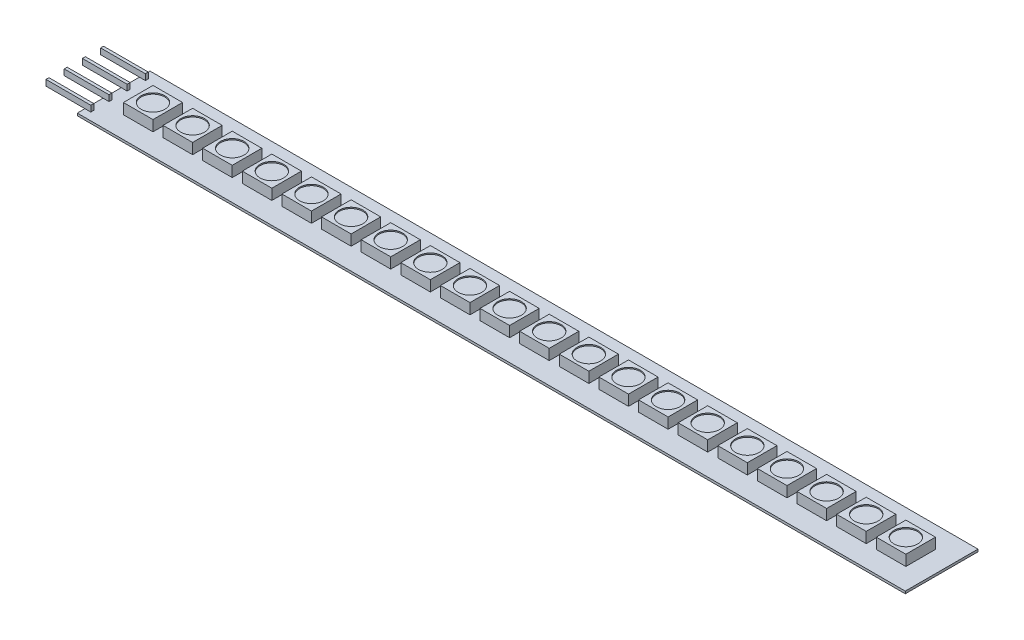
SolidWorks part; units mm, degrees
ref_plane "前基準面" through (0, 0, 0) normal (0, 0, 1) x (1, 0, 0)
ref_plane "上基準面" through (0, 0, 0) normal (0, 1, 0) x (1, 0, 0)
ref_plane "右基準面" through (0, 0, 0) normal (1, 0, 0) x (0, 0, -1)
sketch "草圖1" plane through (0, 0, 0) normal (0, 1, 0) x (1, 0, 0)
  line L1 (0, 0) -> (140, 0)
  line L2 (0, 0) -> (0, 12.3)
  line L3 (0, 12.3) -> (140, 12.3)
  line L4 (140, 0) -> (140, 12.3)
  dimension "D1" = 140
  dimension "D2" = 12.3
extrude "填料-伸長1" add sketch "草圖1" along normal blind 0.4
sketch "草圖2" plane through (0, 0.4, 0) normal (0, 1, 0) x (1, 0, 0)
  line L0 (10, 12.3) -> (10, 0)
  line L1 (140, 12.3) -> (0, 12.3) construction
  line L2 (0, 0) -> (140, 0) construction
  line L3 (0, 12.3) -> (0, 0) construction
  line L4 (16.7, 12.3) -> (16.7, 0)
  line L5 (16.7, 12.3) -> (10, 0) construction
  line L6 (10, 0) -> (10, 12.3) construction
  line L7 (10, 12.3) -> (16.7, 0) construction
  line L8 (9.15, 8.65) -> (4.15, 8.65)
  line L9 (10.85, 3.65) -> (15.85, 3.65)
  line L10 (10.85, 3.65) -> (10.85, 8.65)
  line L11 (10.85, 8.65) -> (15.85, 8.65)
  line L12 (15.85, 3.65) -> (15.85, 8.65)
  line L13 (10.85, 3.65) -> (15.85, 8.65) construction
  line L14 (10.85, 8.65) -> (15.85, 3.65) construction
  line L15 (4.15, 3.65) -> (4.15, 8.65)
  line L16 (9.15, 3.65) -> (4.15, 3.65)
  line L17 (9.15, 3.65) -> (9.15, 8.65)
  line L18 (17.55, 3.65) -> (17.55, 8.65)
  line L19 (17.55, 3.65) -> (22.55, 3.65)
  line L20 (22.55, 3.65) -> (22.55, 8.65)
  line L21 (17.55, 8.65) -> (22.55, 8.65)
  line L22 (23.4, 12.3) -> (23.4, 0)
  line L23 (24.25, 3.65) -> (24.25, 8.65)
  line L24 (24.25, 3.65) -> (29.25, 3.65)
  line L25 (29.25, 3.65) -> (29.25, 8.65)
  line L26 (24.25, 8.65) -> (29.25, 8.65)
  line L27 (30.1, 12.3) -> (30.1, 0)
  line L28 (30.95, 3.65) -> (30.95, 8.65)
  line L29 (30.95, 3.65) -> (35.95, 3.65)
  line L30 (35.95, 3.65) -> (35.95, 8.65)
  line L31 (30.95, 8.65) -> (35.95, 8.65)
  line L32 (36.8, 12.3) -> (36.8, 0)
  line L33 (37.65, 3.65) -> (37.65, 8.65)
  line L34 (37.65, 3.65) -> (42.65, 3.65)
  line L35 (42.65, 3.65) -> (42.65, 8.65)
  line L36 (37.65, 8.65) -> (42.65, 8.65)
  line L37 (43.5, 12.3) -> (43.5, 0)
  line L38 (44.35, 3.65) -> (44.35, 8.65)
  line L39 (44.35, 3.65) -> (49.35, 3.65)
  line L40 (49.35, 3.65) -> (49.35, 8.65)
  line L41 (44.35, 8.65) -> (49.35, 8.65)
  line L42 (50.2, 12.3) -> (50.2, 0)
  line L43 (51.05, 3.65) -> (51.05, 8.65)
  line L44 (51.05, 3.65) -> (56.05, 3.65)
  line L45 (56.05, 3.65) -> (56.05, 8.65)
  line L46 (51.05, 8.65) -> (56.05, 8.65)
  line L47 (56.9, 12.3) -> (56.9, 0)
  line L48 (57.75, 3.65) -> (57.75, 8.65)
  line L49 (57.75, 3.65) -> (62.75, 3.65)
  line L50 (62.75, 3.65) -> (62.75, 8.65)
  line L51 (57.75, 8.65) -> (62.75, 8.65)
  line L52 (63.6, 12.3) -> (63.6, 0)
  line L53 (64.45, 3.65) -> (64.45, 8.65)
  line L54 (64.45, 3.65) -> (69.45, 3.65)
  line L55 (69.45, 3.65) -> (69.45, 8.65)
  line L56 (64.45, 8.65) -> (69.45, 8.65)
  line L57 (70.3, 12.3) -> (70.3, 0)
  line L58 (71.15, 3.65) -> (71.15, 8.65)
  line L59 (71.15, 3.65) -> (76.15, 3.65)
  line L60 (76.15, 3.65) -> (76.15, 8.65)
  line L61 (71.15, 8.65) -> (76.15, 8.65)
  line L62 (77, 12.3) -> (77, 0)
  line L63 (77.85, 3.65) -> (77.85, 8.65)
  line L64 (77.85, 3.65) -> (82.85, 3.65)
  line L65 (82.85, 3.65) -> (82.85, 8.65)
  line L66 (77.85, 8.65) -> (82.85, 8.65)
  line L67 (83.7, 12.3) -> (83.7, 0)
  line L68 (84.55, 3.65) -> (84.55, 8.65)
  line L69 (84.55, 3.65) -> (89.55, 3.65)
  line L70 (89.55, 3.65) -> (89.55, 8.65)
  line L71 (84.55, 8.65) -> (89.55, 8.65)
  line L72 (90.4, 12.3) -> (90.4, 0)
  line L73 (91.25, 3.65) -> (91.25, 8.65)
  line L74 (91.25, 3.65) -> (96.25, 3.65)
  line L75 (96.25, 3.65) -> (96.25, 8.65)
  line L76 (91.25, 8.65) -> (96.25, 8.65)
  line L77 (97.1, 12.3) -> (97.1, 0)
  line L78 (97.95, 3.65) -> (97.95, 8.65)
  line L79 (97.95, 3.65) -> (102.95, 3.65)
  line L80 (102.95, 3.65) -> (102.95, 8.65)
  line L81 (97.95, 8.65) -> (102.95, 8.65)
  line L82 (103.8, 12.3) -> (103.8, 0)
  line L83 (104.65, 3.65) -> (104.65, 8.65)
  line L84 (104.65, 3.65) -> (109.65, 3.65)
  line L85 (109.65, 3.65) -> (109.65, 8.65)
  line L86 (104.65, 8.65) -> (109.65, 8.65)
  line L87 (110.5, 12.3) -> (110.5, 0)
  line L88 (111.35, 3.65) -> (111.35, 8.65)
  line L89 (111.35, 3.65) -> (116.35, 3.65)
  line L90 (116.35, 3.65) -> (116.35, 8.65)
  line L91 (111.35, 8.65) -> (116.35, 8.65)
  line L92 (117.2, 12.3) -> (117.2, 0)
  line L93 (118.05, 3.65) -> (118.05, 8.65)
  line L94 (118.05, 3.65) -> (123.05, 3.65)
  line L95 (123.05, 3.65) -> (123.05, 8.65)
  line L96 (118.05, 8.65) -> (123.05, 8.65)
  line L97 (123.9, 12.3) -> (123.9, 0)
  line L98 (124.75, 3.65) -> (124.75, 8.65)
  line L99 (124.75, 3.65) -> (129.75, 3.65)
  line L100 (129.75, 3.65) -> (129.75, 8.65)
  line L101 (124.75, 8.65) -> (129.75, 8.65)
  line L102 (130.6, 12.3) -> (130.6, 0)
  line L103 (131.45, 3.65) -> (131.45, 8.65)
  line L104 (131.45, 3.65) -> (136.45, 3.65)
  line L105 (136.45, 3.65) -> (136.45, 8.65)
  line L106 (131.45, 8.65) -> (136.45, 8.65)
  line L107 (137.3, 12.3) -> (137.3, 0)
  line L108 (10.85, 3.65) -> (17.55, 3.65) construction
  point P10 (13.35, 6.15)
  dimension "D1" = 10
  dimension "D2" = 6.7
  dimension "D3" = 5
  dimension "D4" = 5
  dimension "D6" = 6.7
  dimension "D5" = 19
extrude "填料-伸長2" add sketch "草圖2" along normal blind 1.8 contours L9 L12 L11 L10 | L21 L18 L19 L20 | L26 L23 L24 L25 | L31 L28 L29 L30 | L36 L33 L34 L35 | L41 L38 L39 L40 | L46 L43 L44 L45 | L51 L48 L49 L50 | L56 L53 L54 L55 | L61 L58 L59 L60 | L66 L63 L64 L65 | L71 L68 L69 L70 | L76 L73 L74 L75 | L81 L78 L79 L80 | L86 L83 L84 L85 | L91 L88 L89 L90 | L96 L93 L94 L95 | L101 L98 L99 L100 | L106 L103 L104 L105 | L15 L8 L17 L16 region at (13.35, 0.4, -6.15) region at (20.05, 0.4, -6.15) region at (26.75, 0.4, -6.15) region at (33.45, 0.4, -6.15) region at (40.15, 0.4, -6.15) region at (46.85, 0.4, -6.15) region at (53.55, 0.4, -6.15) region at (60.25, 0.4, -6.15) region at (66.95, 0.4, -6.15) region at (73.65, 0.4, -6.15) region at (80.35, 0.4, -6.15) region at (87.05, 0.4, -6.15) region at (93.75, 0.4, -6.15) region at (100.45, 0.4, -6.15) region at (107.15, 0.4, -6.15) region at (113.85, 0.4, -6.15) region at (120.55, 0.4, -6.15) region at (127.25, 0.4, -6.15) region at (133.95, 0.4, -6.15)
sketch "草圖3" plane through (0, 2.2, 0) normal (0, 1, 0) x (1, 0, 0)
  line L0 (4.15, 3.65) -> (9.15, 8.65) construction
  line L1 (9.15, 8.65) -> (9.15, 3.65) construction
  line L2 (9.15, 3.65) -> (4.15, 8.65) construction
  line L3 (6.65, 6.15) -> (13.35, 6.15) construction
  circle A0 centre (6.65, 6.15) radius 2
  circle A1 centre (13.35, 6.15) radius 2
  circle A2 centre (20.05, 6.15) radius 2
  circle A3 centre (26.75, 6.15) radius 2
  circle A4 centre (33.45, 6.15) radius 2
  circle A5 centre (40.15, 6.15) radius 2
  circle A6 centre (46.85, 6.15) radius 2
  circle A7 centre (53.55, 6.15) radius 2
  circle A8 centre (60.25, 6.15) radius 2
  circle A9 centre (66.95, 6.15) radius 2
  circle A10 centre (73.65, 6.15) radius 2
  circle A11 centre (80.35, 6.15) radius 2
  circle A12 centre (87.05, 6.15) radius 2
  circle A13 centre (93.75, 6.15) radius 2
  circle A14 centre (100.45, 6.15) radius 2
  circle A15 centre (107.15, 6.15) radius 2
  circle A16 centre (113.85, 6.15) radius 2
  circle A17 centre (120.55, 6.15) radius 2
  circle A18 centre (127.25, 6.15) radius 2
  circle A19 centre (133.95, 6.15) radius 2
  dimension "D1" = 4
  dimension "D3" = 6.7
  dimension "D2" = 20
extrude "除料-伸長1" cut sketch "草圖3" against normal blind 0.2
sketch "草圖4" plane through (0, 0.4, 0) normal (0, 1, 0) x (1, 0, 0)
  line L0 (0, 12.3) -> (0, 0) construction
  line L2 (0, 10.5125) -> (-6.576, 10.5125)
  line L3 (0, 10.5125) -> (0, 11.0125)
  line L4 (0, 11.0125) -> (-6.576, 11.0125)
  line L5 (-6.576, 10.5125) -> (-6.576, 11.0125)
  line L6 (0, 0) -> (0, 3.075)
  line L7 (0, 7.4375) -> (-6.576, 7.4375)
  line L8 (0, 7.4375) -> (0, 7.9375)
  line L9 (0, 7.9375) -> (-6.576, 7.9375)
  line L10 (-6.576, 7.4375) -> (-6.576, 7.9375)
  line L11 (0, 4.8625) -> (-6.576, 4.8625)
  line L12 (0, 4.8625) -> (0, 4.3625)
  line L13 (0, 4.3625) -> (-6.576, 4.3625)
  line L14 (-6.576, 4.8625) -> (-6.576, 4.3625)
  line L15 (0, 1.7875) -> (-6.576, 1.7875)
  line L16 (0, 1.7875) -> (0, 1.2875)
  line L17 (0, 1.2875) -> (-6.576, 1.2875)
  line L18 (-6.576, 1.7875) -> (-6.576, 1.2875)
  line L19 (0, 3.075) -> (0, 6.15)
  line L20 (0, 6.15) -> (0, 9.225)
  line L21 (0, 9.225) -> (0, 12.3)
  line L23 (0, 11.0125) -> (1, 11.0125)
  line L24 (0, 11.0125) -> (0, 10.5125)
  line L25 (0, 10.5125) -> (1, 10.5125)
  line L26 (1, 11.0125) -> (1, 10.5125)
  line L27 (0, 7.9375) -> (1, 7.9375)
  line L28 (0, 7.9375) -> (0, 7.4375)
  line L29 (0, 7.4375) -> (1, 7.4375)
  line L30 (1, 7.9375) -> (1, 7.4375)
  line L31 (0, 4.8625) -> (1, 4.8625)
  line L32 (0, 4.8625) -> (0, 4.3625)
  line L33 (0, 4.3625) -> (1, 4.3625)
  line L34 (1, 4.8625) -> (1, 4.3625)
  line L35 (0, 1.7875) -> (1, 1.7875)
  line L36 (0, 1.7875) -> (0, 1.2875)
  line L37 (0, 1.2875) -> (1, 1.2875)
  line L38 (1, 1.7875) -> (1, 1.2875)
  point P23 (0, 1.5375)
  point P28 (0, 1.5375)
  point P29 (0, 4.6125)
  point P30 (0, 4.6125)
  point P31 (0, 10.7625)
  point P32 (0, 10.7625)
  point P33 (0, 7.6875)
  point P34 (0, 7.6875)
  dimension "D1" = 3.075
  dimension "D2" = 3.075
  dimension "D3" = 0.5
  dimension "D4" = 0.5
  dimension "D5" = 0.5
  dimension "D6" = 0.5
  dimension "D7" = 1
extrude "填料-伸長3" add sketch "草圖4" along normal blind 1 contours L10 L7 L8 L9 | L30 L27 L8 L29 | L5 L2 L3 L4 | L26 L23 L3 L25 | L11 L14 L13 L12 | L34 L31 L12 L33 | L15 L18 L17 L6 | L38 L35 L6 L37 region at (-3.288, 0.4, -10.7625) region at (0.5, 0.4, -1.5375) region at (-3.288, 0.4, -1.5375) region at (0.5, 0.4, -4.6125) region at (-3.288, 0.4, -4.6125) region at (0.5, 0.4, -7.6875) region at (-3.288, 0.4, -7.6875) region at (0.5, 0.4, -10.7625)
